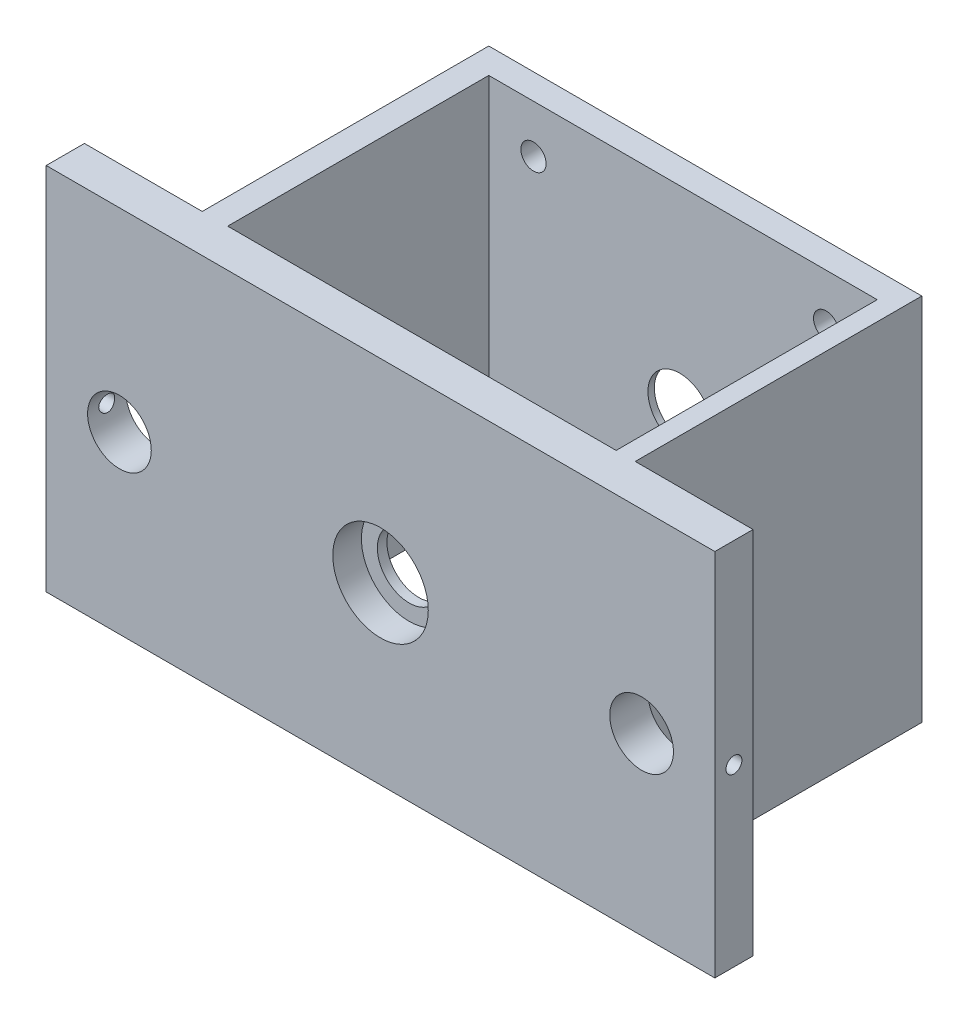
SolidWorks part; units mm, degrees
ref_plane "Front Plane" through (0, 0, 0) normal (0, 0, 1) x (1, 0, 0)
ref_plane "Top Plane" through (0, 0, 0) normal (0, 1, 0) x (1, 0, 0)
ref_plane "Right Plane" through (0, 0, 0) normal (1, 0, 0) x (0, 0, -1)
sketch "Sketch1" plane through (0, 0, 0) normal (0, 1, 0) x (1, 0, 0)
  line L1 (0, 0) -> (210, 0)
  line L2 (0, 0) -> (0, 12)
  line L3 (0, 12) -> (210, 12)
  line L4 (210, 0) -> (210, 12)
  dimension "D1" = 12
  dimension "D2" = 210
extrude "Boss-Extrude1" add sketch "Sketch1" along normal blind 116
sketch "Sketch2" plane through (0, 0, 0) normal (0, 0, 1) x (1, 0, 0)
  line L0 (0, 0) -> (210, 0) construction
  line L1 (0, 116) -> (0, 0) construction
  line L2 (210, 116) -> (210, 0) construction
  circle A0 centre (23, 55) radius 10
  circle A1 centre (187, 55) radius 10
  dimension "D1" = 55
  dimension "D2" = 55
  dimension "D3" = 23
  dimension "D4" = 23
extrude "Cut-Extrude1" cut sketch "Sketch2" against normal through all
hole_wizard "Ø5.0mm Dowel Hole1" positions "Sketch4" profile "Sketch3" hole size "Ø5.0" standard "ANSI Metric"
sketch "Sketch4" plane through (0, 0, 0) normal (-1, 0, 0) x (0, 0, 1)
  line L0 (-12, 116) -> (-12, 0) construction
  line L1 (-12, 0) -> (0, 0) construction
  point P0 (-6, 55)
  dimension "D1" = 6
  dimension "D2" = 55
sketch "Sketch3" plane through (0, 55, -6) normal (0, 1, 0) x (0, 0, 1)
  line L0 (0, 0) -> (0, 26.5022)
  line L1 (0, 26.5022) -> (2.5, 25)
  line L2 (2.5, 25) -> (2.5, 0)
  line L5 (2.5, 0) -> (0, 0)
  line L10 (0, 26.5022) -> (-2.5, 25) construction
  line L11 (0, -6.35) -> (0, 107.95) construction
  dimension "Hole Dia." = 5
  dimension "Hole Depth" = 25
  dimension "Drill Angle" = 118
hole_wizard "Ø5.0mm Dowel Hole2" positions "Sketch6" profile "Sketch5" hole size "Ø5.0" standard "ANSI Metric"
sketch "Sketch6" plane through (210, 0, 0) normal (1, 0, 0) x (0, 0, -1)
  line L0 (0, 0) -> (12, 0) construction
  line L1 (0, 116) -> (0, 0) construction
  point P0 (6, 55)
  dimension "D1" = 55
  dimension "D2" = 6
sketch "Sketch5" plane through (210, 55, -6) normal (0, 1, 0) x (0, 0, -1)
  line L0 (0, 0) -> (0, 26.5022)
  line L1 (0, 26.5022) -> (2.5, 25)
  line L2 (2.5, 25) -> (2.5, 0)
  line L5 (2.5, 0) -> (0, 0)
  line L10 (0, 26.5022) -> (-2.5, 25) construction
  line L11 (0, -6.35) -> (0, 107.95) construction
  dimension "Hole Dia." = 5
  dimension "Hole Depth" = 25
  dimension "Drill Angle" = 118
sketch "Sketch7" plane through (0, 0, 0) normal (0, 0, 1) x (1, 0, 0)
  line L0 (0, 0) -> (210, 0) construction
  line L1 (0, 116) -> (0, 0) construction
  circle A0 centre (105, 55) radius 10
  dimension "D1" = 20
  dimension "D2" = 55
  dimension "D3" = 105
hole_wizard "Ø5.0mm Dowel Hole3" positions "Sketch10" profile "Sketch9" hole size "Ø5.0" standard "ANSI Metric"
sketch "Sketch10" plane through (0, 0, 0) normal (0, -1, 0) x (-1, 0, 0)
  line L0 (-210, 12) -> (0, 12) construction
  line L1 (-210, 0) -> (-210, 12) construction
  line L2 (0, 12) -> (0, 0) construction
  point P0 (-25, 6)
  point P2 (-105, 6)
  point P4 (-185, 6)
  dimension "D1" = 6
  dimension "D2" = 6
  dimension "D3" = 6
  dimension "D4" = 25
  dimension "D5" = 25
  dimension "D6" = 105
sketch "Sketch9" plane through (25, 0, -6) normal (1, 0, 0) x (0, 0, -1)
  line L0 (0, 0) -> (0, 26.5022)
  line L1 (0, 26.5022) -> (2.5, 25)
  line L2 (2.5, 25) -> (2.5, 0)
  line L5 (2.5, 0) -> (0, 0)
  line L10 (0, 26.5022) -> (-2.5, 25) construction
  line L11 (0, -6.35) -> (0, 107.95) construction
  dimension "Hole Dia." = 5
  dimension "Hole Depth" = 25
  dimension "Drill Angle" = 118
sketch "Sketch11" plane through (0, 0, -12) normal (0, 0, -1) x (-1, 0, 0)
  line L0 (-210, 0) -> (0, 0) construction
  line L1 (-37, 0) -> (-45, 0)
  line L2 (-37, 0) -> (-37, 116)
  line L3 (-37, 116) -> (-45, 116)
  line L4 (-45, 0) -> (-45, 116)
  line L5 (-210, 116) -> (0, 116) construction
  line L6 (-210, 116) -> (-210, 0) construction
  line L7 (-167, 0) -> (-173, 0)
  line L8 (-167, 0) -> (-167, 116)
  line L9 (-167, 116) -> (-173, 116)
  line L10 (-173, 0) -> (-173, 116)
  line L11 (0, 116) -> (0, 0) construction
  dimension "D1" = 6
  dimension "D2" = 8
  dimension "D3" = 37
  dimension "D4" = 37
extrude "Boss-Extrude2" add sketch "Sketch11" along normal blind 90
sketch "Sketch12" plane through (167, 0, 0) normal (-1, 0, 0) x (0, 0, 1)
  line L0 (-102, 0) -> (-102, 116) construction
  line L1 (-102, 0) -> (-94, 0)
  line L2 (-102, 0) -> (-102, 116)
  line L3 (-102, 116) -> (-94, 116)
  line L4 (-94, 0) -> (-94, 116)
  line L5 (-102, 0) -> (-12, 0) construction
  line L6 (-102, 116) -> (-12, 116) construction
  dimension "D1" = 8
extrude "Boss-Extrude4" add sketch "Sketch12" along normal up to next
extrude "Cut-Extrude3" cut sketch "Sketch7" against normal through all
sketch "Sketch13" plane through (0, 0, -102) normal (0, 0, -1) x (-1, 0, 0)
  circle A0 centre (-105, 55) radius 47.5
  dimension "D1" = 95
extrude "Cut-Extrude4" cut sketch "Sketch13" against normal blind 6
hole_wizard "5/16 (0.3125) Diameter Hole1" positions "Sketch15" profile "Sketch14" hole size "5/16" standard "ANSI Inch"
sketch "Sketch15" plane through (0, 0, -102) normal (0, 0, -1) x (-1, 0, 0)
  line L2 (-105, 116) -> (-105, 36.0838) construction
  line L3 (-37, 116) -> (-173, 116) construction
  line L5 (-105, 55) -> (-150.9619, 100.9619) construction
  circle A0 centre (-105, 55) radius 10 construction
  point P0 (-150.9619, 100.9619)
  dimension "D1" = 65
  dimension "D2" = 45
sketch "Sketch14" plane through (150.9619, 100.9619, -102) normal (1, 0, 0) x (0, 1, 0)
  line L0 (0, 0) -> (0, 14.3847)
  line L1 (0, 14.3847) -> (3.9687, 12)
  line L2 (3.9687, 12) -> (3.9687, 0)
  line L5 (3.9687, 0) -> (0, 0)
  line L10 (0, 14.3847) -> (-3.9688, 12) construction
  line L11 (0, -6.35) -> (0, 107.95) construction
  dimension "Hole Dia." = 7.9375
  dimension "Hole Depth" = 12
  dimension "Drill Angle" = 118
ref_axis "Axis1" through (105, 55, -96) along (0, 0, 1)
pattern_circular "CirPattern1" count 4 over 360 about axis through (105, 55, -96) along (0, 0, 1) of "5/16 (0.3125) Diameter Hole1"
sketch "Sketch16" plane through (0, 0, 0) normal (0, 0, 1) x (1, 0, 0)
  circle A0 centre (105, 55) radius 15
  dimension "D1" = 30
extrude "Cut-Extrude5" cut sketch "Sketch16" against normal blind 9
